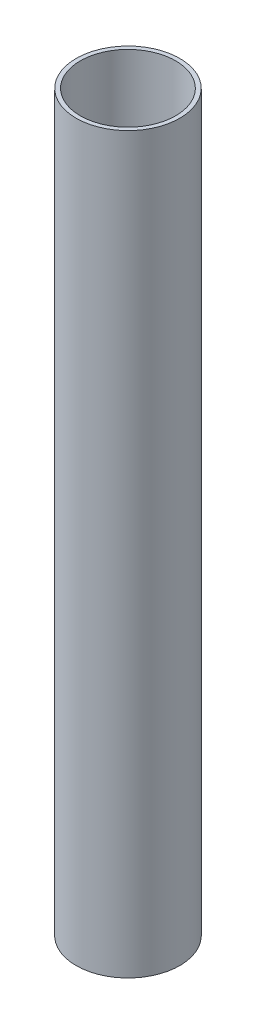
SolidWorks part; units mm, degrees
material "ПВХ 0.007 Смягченный"
ref_plane "Спереди" through (0, 0, 0) normal (0, 0, 1) x (1, 0, 0)
ref_plane "Сверху" through (0, 0, 0) normal (0, 1, 0) x (1, 0, 0)
ref_plane "Справа" through (0, 0, 0) normal (1, 0, 0) x (0, 0, -1)
sketch "Эскиз1" plane through (0, 0, 0) normal (0, 1, 0) x (1, 0, 0)
  circle A0 centre (0, 0) radius 25
  circle A1 centre (0, 0) radius 23
  dimension "ExDBody" = 50
  dimension "InDBody" = 46
extrude "Бобышка-Вытянуть1" add sketch "Эскиз1" along normal blind 354
